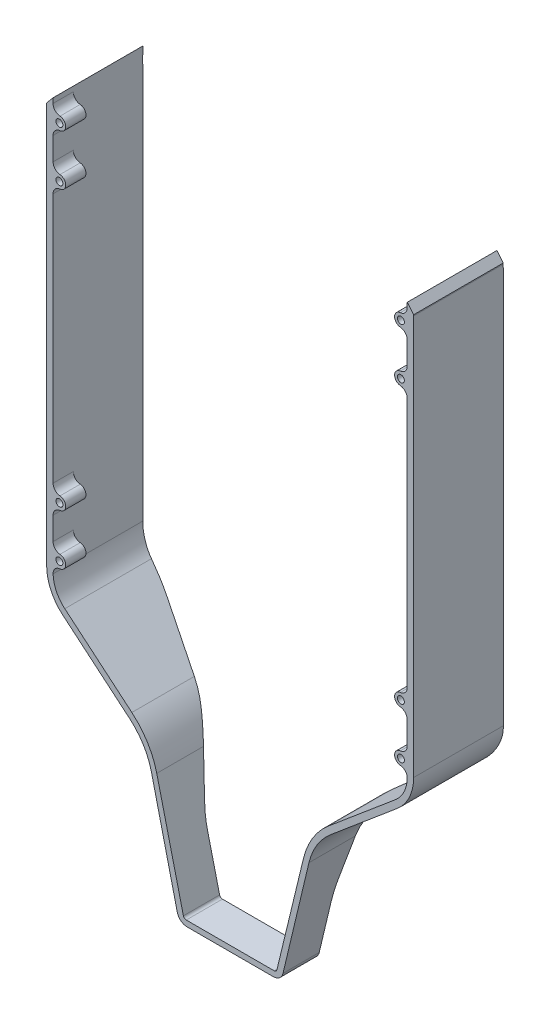
SolidWorks part; units mm, degrees
ref_plane "Front Plane" through (0, 0, 0) normal (1, 0, 0) x (0, 1, 0)
ref_plane "Top Plane" through (0, 0, 0) normal (0, 0, 1) x (0, 1, 0)
ref_plane "Right Plane" through (0, 0, 0) normal (0, 1, 0) x (-1, 0, 0)
ref_plane "Plane3" through (0, 0, 60) normal (0, 0, 1) x (0, 1, 0)
sketch "Sketch6" plane through (0, 0, 60) normal (0, 0, 1) x (0, 1, 0)
  line L2 (-172.2576, 12.3464) -> (-172.2578, 12.3467) construction
  line L3 (142.2079, -16.3566) -> (140.1905, -14.8218) construction
  line L4 (135.1067, 16.7401) -> (132.5719, 16.7401) construction
  line L6 (136.8412, 8.5049) -> (134.8324, 6.959) construction
  line L7 (-169.1778, -25.9561) -> (-125.6714, -36.4849)
  line L9 (-79.3544, 69.1337) -> (-77.414, 67.5026) construction
  line L16 (-102.5567, -58.7822) -> (-90.1043, -73.596)
  line L17 (-102.5567, -58.7822) -> (-112.3143, -47.1743)
  line L18 (-79.3544, -84.0811) -> (-77.414, -82.45) construction
  line L19 (-87.4882, -72.8387) -> (-109.7635, -46.3393)
  line L24 (81.7065, -80.0137) -> (-76.3257, -80.0137)
  line L25 (-77.537, -77.4737) -> (83.5853, -77.4737)
  line L31 (136.8412, -23.4523) -> (134.8324, -21.9064) construction
  line L35 (99.934, -71.0407) -> (133.6845, -27.1831)
  line L36 (130.3109, -28.3617) -> (96.9718, -70.9523)
  line L37 (135.1067, -31.6875) -> (132.5719, -31.6875) construction
  line L38 (134.7427, 9.1253) -> (134.7427, -24.0727)
  line L40 (132.5427, -21.8896) -> (132.5427, 6.9422)
  line L54 (-126.1898, -38.6125) -> (-169.1845, -28.3669)
  line L55 (-172.2576, -27.2938) -> (-172.2578, -27.2941) construction
  line L56 (-170.0573, 9.891) -> (-170.0573, -24.8384)
  line L57 (-172.2573, 9.5285) -> (-172.2573, -24.4759)
  line L58 (142.2079, 1.4092) -> (140.1905, -0.1256) construction
  line L59 (-126.1898, 23.6651) -> (-169.1845, 13.4195)
  line L61 (130.3109, 13.4143) -> (96.9718, 56.005)
  line L62 (99.934, 56.0933) -> (133.6845, 12.2357)
  line L63 (-77.537, 62.5263) -> (83.5853, 62.5263)
  line L64 (81.7065, 65.0663) -> (-76.3257, 65.0663)
  line L65 (-87.4882, 57.8913) -> (-109.7635, 31.3919)
  line L66 (-102.5567, 43.8348) -> (-112.3143, 32.2269)
  line L67 (-102.5567, 43.8348) -> (-90.1043, 58.6486)
  line L68 (-169.1778, 11.0087) -> (-125.6714, 21.5375)
  line L69 (-172.2573, -7.4737) -> (134.7427, -7.4737) construction
  arc A6 (-109.7635, -46.3393) -> (-125.6714, -36.4849) centre (-132.7279, -65.6432) ccw
  arc A7 (-112.3143, -47.1743) -> (-126.1898, -38.6125) centre (-132.2168, -63.9043) ccw
  arc A10 (-76.3257, -80.0137) -> (-90.1043, -73.596) centre (-76.3257, -62.0137) cw
  arc A11 (-87.4882, -72.8387) -> (-77.537, -77.4737) centre (-77.537, -64.4737) ccw
  arc A14 (81.7065, -80.0137) -> (99.934, -71.0407) centre (81.7065, -57.0137) ccw
  arc A15 (83.5853, -77.4737) -> (96.9718, -70.9523) centre (83.5853, -60.4737) ccw
  arc A16 (130.3109, -28.3617) -> (132.5427, -21.8896) centre (122.0427, -21.8896) ccw
  arc A17 (133.6845, -27.1831) -> (134.7427, -24.0727) centre (129.6427, -24.0727) ccw
  arc A37 (-169.1845, -28.3669) -> (-172.2573, -24.4759) centre (-168.2573, -24.4759) cw
  arc A38 (-170.0573, -24.8384) -> (-169.1778, -25.9561) centre (-168.9073, -24.8384) ccw
  arc A41 (-170.0573, 9.891) -> (-169.1778, 11.0087) centre (-168.9073, 9.891) cw
  arc A42 (-169.1845, 13.4195) -> (-172.2573, 9.5285) centre (-168.2573, 9.5285) ccw
  arc A43 (133.6845, 12.2357) -> (134.7427, 9.1253) centre (129.6427, 9.1253) cw
  arc A44 (130.3109, 13.4143) -> (132.5427, 6.9422) centre (122.0427, 6.9422) cw
  arc A45 (83.5853, 62.5263) -> (96.9718, 56.005) centre (83.5853, 45.5263) cw
  arc A46 (81.7065, 65.0663) -> (99.934, 56.0933) centre (81.7065, 42.0663) cw
  arc A47 (-87.4882, 57.8913) -> (-77.537, 62.5263) centre (-77.537, 49.5263) cw
  arc A48 (-76.3257, 65.0663) -> (-90.1043, 58.6486) centre (-76.3257, 47.0663) ccw
  arc A49 (-112.3143, 32.2269) -> (-126.1898, 23.6651) centre (-132.2168, 48.9569) cw
  arc A50 (-109.7635, 31.3919) -> (-125.6714, 21.5375) centre (-132.7279, 50.6958) cw
  point P81 (132.5427, -7.4737)
  point P85 (134.7427, -7.4737)
  point P86 (-173.0573, -7.4737)
  point P94 (-170.0573, -7.4737)
  point P98 (134.7427, -7.4737)
  point P105 (-172.2573, -7.4737)
  point P106 (132.5427, -7.4737)
  dimension "D6" = 2.54
  dimension "D10" = 4
  dimension "D12" = 30
  dimension "D13" = 26
  dimension "D15" = 307
  dimension "D18" = 18
  dimension "D19" = 13
  dimension "D24" = 23
  dimension "D25" = 17
  dimension "D27" = 10.5
  dimension "D28" = 5.1
  dimension "D14" = 1.15
  dimension "D8" = 2.2
  dimension "D11" = 2.5349
  dimension "D23" = 2.5349
  dimension "D26" = 2.5349
extrude "Boss-Extrude4" add sketch "Sketch6" against normal blind 60 contours L24 A10 L16 L17 A7 L54 A37 L57 A42 L59 A49 L66 L67 A48 L64 A46 L62 A43 L38 A17 L35 A14 | L25 A15 L36 A16 L40 A44 L61 A45 L63 A47 L65 A50 L68 A41 L56 A38 L7 A6 L19 A11
sketch "Sketch7" plane through (0, 0, 0) normal (1, 0, 0) x (0, 1, 0)
  line L0 (-173.3168, 60) -> (-173.3168, 15.4252) construction
  line L2 (135.254, 60) -> (135.254, 9.6153) construction
  line L3 (136.8412, 60) -> (134.8324, 60) construction
  line L4 (-175.2573, 60) -> (-175.2573, 0) construction
  line L5 (-173.3168, 29.8073) -> (-149.3495, 29.8073)
  line L6 (-133.5324, 27.3305) -> (-140.9911, 28.9242)
  line L7 (118.253, 28.0043) -> (110.0984, 20.7035)
  line L8 (-116.6775, 22.6341) -> (-95.0112, 12.5187)
  line L10 (-173.3168, 29.8073) -> (-175.2573, 29.8073)
  line L11 (-77.6666, 8.6692) -> (78.6149, 8.6692)
  line L12 (-175.2573, 29.8073) -> (-175.2573, -52.4358)
  line L13 (126.7242, 31.2423) -> (135.254, 31.2423)
  line L14 (-133.5324, 27.3305) -> (-125.6688, 25.6502)
  line L15 (-175.2573, -52.4358) -> (135.254, -52.4358)
  line L16 (135.254, -52.4358) -> (135.254, 31.2423)
  arc A0 (-149.3495, 29.8073) -> (-140.9911, 28.9242) centre (-149.3495, -10.1927) cw
  arc A1 (-116.6775, 22.6341) -> (-125.6688, 25.6502) centre (-134.4451, -15.4226) ccw
  arc A2 (-95.0112, 12.5187) -> (-77.6666, 8.6692) centre (-77.6666, 49.6692) ccw
  arc A3 (78.6149, 8.6692) -> (110.0984, 20.7035) centre (78.6149, 55.8692) ccw
  arc A4 (118.253, 28.0043) -> (126.7242, 31.2423) centre (126.7242, 18.5423) cw
  dimension "D1" = 40
  dimension "D2" = 42
  dimension "D3" = 41
  dimension "D4" = 47.2
  dimension "D5" = 12.7
extrude "Cut-Extrude1" cut sketch "Sketch7" against normal through all both and the other way through all
ref_plane "Plane4" through (0, 0, 60) normal (0, 0, 1) x (0, -1, 0)
sketch "Sketch8" plane through (0, 0, 60) normal (0, 0, 1) x (0, -1, 0)
  line L1 (188.6815, -113.5253) -> (-188.6815, -113.5253)
  line L2 (188.6815, -113.5253) -> (188.6815, 113.5253)
  line L3 (188.6815, 113.5253) -> (-188.6815, 113.5253)
  line L4 (-188.6815, -113.5253) -> (-188.6815, 113.5253)
  line L5 (188.6815, -113.5253) -> (-188.6815, 113.5253) construction
  line L6 (188.6815, 113.5253) -> (-188.6815, -113.5253) construction
  point P0 (0, 0)
extrude "Cut-Extrude2" cut sketch "Sketch8" against normal blind 15.88
sketch "Sketch9" plane through (0, 0, 60) normal (0, 0, 1) x (0, -1, 0)
  line L0 (-134.7427, 7.4737) -> (-82.1027, 7.4737) construction
  line L1 (-134.7427, 24.0727) -> (-134.7427, -9.1253) construction
  line L2 (-82.1027, 147.5495) -> (-82.1027, -132.6021)
  line L3 (-82.1027, -132.6021) -> (-212.4759, -132.6021)
  line L4 (-212.4759, -132.6021) -> (-212.4759, 147.5495)
  line L5 (-212.4759, 147.5495) -> (-82.1027, 147.5495)
  point P7 (-82.1027, 7.4737)
  dimension "D1" = 52.64
extrude "Cut-Extrude3" cut sketch "Sketch9" along normal through all both and the other way through all
sketch "Sketch10" plane through (0, 0, 8.6692) normal (0, 0, -1) x (1, 0, 0)
  line L0 (80.0103, -82.1027) -> (77.4737, -82.1027)
  line L1 (77.4737, -82.1027) -> (77.4737, -85.1027)
  line L2 (77.4737, -85.1027) -> (80.0103, -82.1027)
  line L3 (7.4737, 172.2573) -> (7.4737, -208.3939) construction
  line L4 (24.4759, 172.2573) -> (-9.5285, 172.2573) construction
  line L5 (-62.5263, -82.1027) -> (-62.5263, -85.1027)
  line L6 (-65.0629, -82.1027) -> (-62.5263, -82.1027)
  line L7 (-62.5263, -85.1027) -> (-65.0629, -82.1027)
  dimension "D1" = 3
extrude "Boss-Extrude5" add sketch "Sketch10" against normal up to surface (35.4508 mm away) up to face at (7.4737, -82.7184, 44.12)
ref_plane "Plane5" through (0, 0, 44.12) normal (0, 0, 1) x (0, -1, 0)
sketch "Sketch12" plane through (0, 0, 44.12) normal (0, 0, 1) x (0, -1, 0)
  line L0 (172.2573, 7.4737) -> (50172.2573, 7.4737) construction
  line L1 (172.2573, 24.4759) -> (172.2573, -9.5285) construction
  line L2 (-2.6904, 80.0137) -> (-2.6904, 7.4737) construction
  line L3 (76.3257, 80.0137) -> (-81.7065, 80.0137) construction
  line L4 (72.3096, 77.4737) -> (72.3096, 74.9737) construction
  line L5 (-85.1027, 77.4737) -> (77.537, 77.4737) construction
  line L6 (69.8096, 74.9737) -> (69.8096, 77.4737)
  line L7 (74.8096, 74.9737) -> (74.8096, 77.4737)
  line L8 (74.8096, 77.4737) -> (69.8096, 77.4737)
  line L9 (49.8096, 74.9737) -> (49.8096, 77.4737)
  line L10 (54.8096, 77.4737) -> (49.8096, 77.4737)
  line L11 (54.8096, 74.9737) -> (54.8096, 77.4737)
  line L12 (-80.1904, 74.9737) -> (-80.1904, 77.4737)
  line L13 (-80.1904, 77.4737) -> (-75.1904, 77.4737)
  line L14 (-75.1904, 74.9737) -> (-75.1904, 77.4737)
  line L15 (-60.1904, 74.9737) -> (-60.1904, 77.4737)
  line L16 (-60.1904, 77.4737) -> (-55.1904, 77.4737)
  line L17 (-55.1904, 74.9737) -> (-55.1904, 77.4737)
  line L18 (74.8096, -60.0263) -> (74.8096, -62.5263)
  line L19 (74.8096, -62.5263) -> (69.8096, -62.5263)
  line L20 (69.8096, -60.0263) -> (69.8096, -62.5263)
  line L21 (54.8096, -60.0263) -> (54.8096, -62.5263)
  line L22 (54.8096, -62.5263) -> (49.8096, -62.5263)
  line L23 (49.8096, -60.0263) -> (49.8096, -62.5263)
  line L24 (-55.1904, -60.0263) -> (-55.1904, -62.5263)
  line L25 (-60.1904, -62.5263) -> (-55.1904, -62.5263)
  line L26 (-60.1904, -60.0263) -> (-60.1904, -62.5263)
  line L27 (-75.1904, -60.0263) -> (-75.1904, -62.5263)
  line L28 (-80.1904, -62.5263) -> (-75.1904, -62.5263)
  line L29 (-80.1904, -60.0263) -> (-80.1904, -62.5263)
  arc A0 (69.8096, 74.9737) -> (74.8096, 74.9737) centre (72.3096, 74.9737) ccw
  arc A1 (49.8096, 74.9737) -> (54.8096, 74.9737) centre (52.3096, 74.9737) ccw
  arc A2 (-75.1904, 74.9737) -> (-80.1904, 74.9737) centre (-77.6904, 74.9737) cw
  arc A3 (-55.1904, 74.9737) -> (-60.1904, 74.9737) centre (-57.6904, 74.9737) cw
  arc A4 (69.8096, -60.0263) -> (74.8096, -60.0263) centre (72.3096, -60.0263) cw
  arc A5 (49.8096, -60.0263) -> (54.8096, -60.0263) centre (52.3096, -60.0263) cw
  arc A6 (-55.1904, -60.0263) -> (-60.1904, -60.0263) centre (-57.6904, -60.0263) ccw
  arc A7 (-75.1904, -60.0263) -> (-80.1904, -60.0263) centre (-77.6904, -60.0263) ccw
  circle A8 centre (-77.6904, 74.9737) radius 1.375
  circle A9 centre (-57.6904, 74.9737) radius 1.375
  circle A10 centre (52.3096, 74.9737) radius 1.375
  circle A11 centre (72.3096, 74.9737) radius 1.375
  circle A12 centre (72.3096, -60.0263) radius 1.375
  circle A13 centre (52.3096, -60.0263) radius 1.375
  circle A14 centre (-57.6904, -60.0263) radius 1.375
  circle A15 centre (-77.6904, -60.0263) radius 1.375
  point P4 (172.2573, 7.4737)
  dimension "D1" = 2.5
  dimension "D2" = 75
  dimension "D5" = 2.75
  dimension "D4" = 55
  dimension "D3" = 2
extrude "Boss-Extrude6" add sketch "Sketch12" against normal blind 8
fillet "Fillet1" radius 3 16 edges at (77.4737, -69.8096, 40.12) (77.4737, -74.8096, 40.12) (77.4737, -54.8096, 40.12) (77.4737, -49.8096, 40.12) (77.4737, 55.1904, 40.12) (77.4737, 60.1904, 40.12) (77.4737, 75.1904, 40.12) (77.4737, 80.1904, 40.12) (-62.5263, 80.1904, 40.12) (-62.5263, 75.1904, 40.12) (-62.5263, 60.1904, 40.12) (-62.5263, 55.1904, 40.12) (-62.5263, -49.8096, 40.12) (-62.5263, -54.8096, 40.12) (-62.5263, -74.8096, 40.12) (-62.5263, -69.8096, 40.12)
ref_plane "Plane6" through (0, 0, 8.6692) normal (0, 0, -1) x (0, 1, 0)
